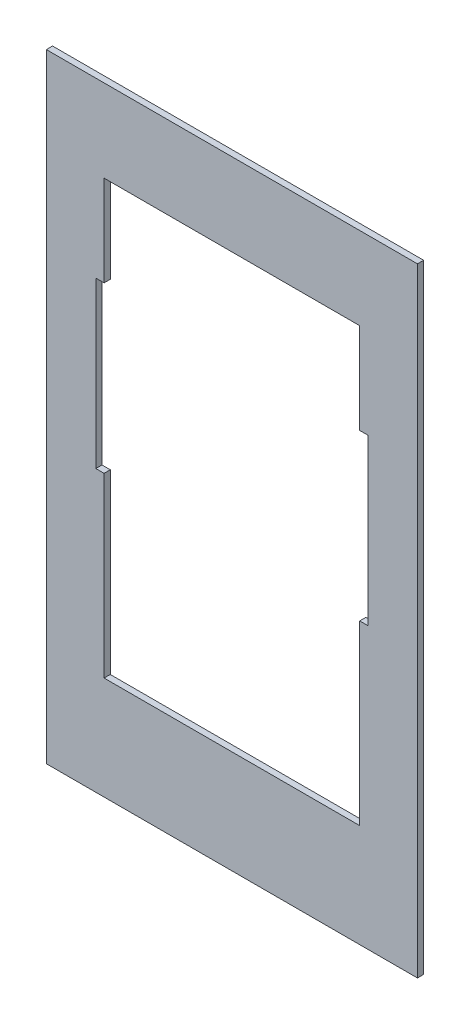
SolidWorks part; units mm, degrees
ref_plane "Front Plane" through (0, 0, 0) normal (0, 0, 1) x (1, 0, 0)
ref_plane "Top Plane" through (0, 0, 0) normal (0, 1, 0) x (1, 0, 0)
ref_plane "Right Plane" through (0, 0, 0) normal (1, 0, 0) x (0, 0, -1)
sketch "Sketch1" plane through (0, 0, 0) normal (0, 0, 1) x (1, 0, 0)
  line L1 (-45, 75) -> (45, 75)
  line L2 (-45, 75) -> (-45, -75)
  line L3 (-45, -75) -> (45, -75)
  line L4 (45, 75) -> (45, -75)
  line L5 (-45, 75) -> (45, -75) construction
  line L6 (-45, -75) -> (45, 75) construction
  line L20 (0, 0) -> (0, 97.4562) construction
  line L21 (0, 0) -> (0, -80.4119) construction
  line L22 (-31, -7) -> (-31, -50)
  line L23 (-31, 55) -> (31, 55)
  line L24 (-31, 55) -> (-31, 33)
  line L25 (-31, -50) -> (31, -50)
  line L26 (31, 55) -> (31, 33)
  line L27 (-31, 55) -> (31, -50) construction
  line L28 (-31, -50) -> (31, 55) construction
  line L29 (-31, 33) -> (-33, 33)
  line L31 (-31, -7) -> (-33, -7)
  line L32 (-33, 33) -> (-33, -7)
  line L33 (31, 33) -> (33, 33)
  line L35 (31, -7) -> (33, -7)
  line L36 (33, 33) -> (33, -7)
  line L37 (31, -7) -> (31, -50)
  point P0 (0, 0)
  point P6 (0, 2.5)
  dimension "D1" = 62
  dimension "D2" = 90
  dimension "D3" = 2
  dimension "D4" = 2
  dimension "D5" = 150
  dimension "D6" = 20
  dimension "D7" = 40
  dimension "D8" = 40
  dimension "D9" = 25
  dimension "D10" = 22
  dimension "D11" = 22
extrude "Boss-Extrude1" add sketch "Sketch1" along normal blind 1.5
